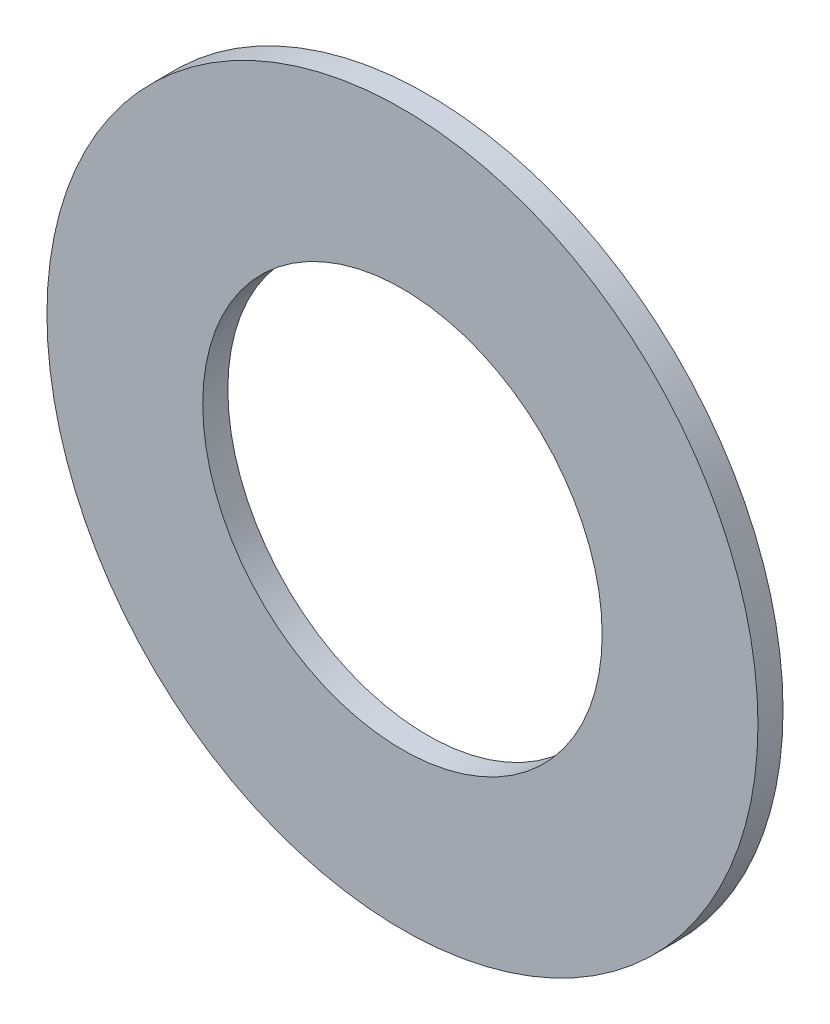
SolidWorks part; units mm, degrees
ref_plane "Front Plane" through (0, 0, 0) normal (0, 0, 1) x (1, 0, 0)
ref_plane "Top Plane" through (0, 0, 0) normal (0, 1, 0) x (1, 0, 0)
ref_plane "Right Plane" through (0, 0, 0) normal (1, 0, 0) x (0, 0, -1)
sketch "Sketch1" plane through (0, 0, 0) normal (0, 0, 1) x (1, 0, 0)
  circle A0 centre (0, 0) radius 12.5 construction
  circle A1 centre (0, 0) radius 22.25 construction
  point P4 (0, -12.5)
  dimension "ID" = 25
  dimension "OD" = 44.5
sketch "Sketch2" plane through (0, 0, 0) normal (1, 0, 0) x (0, 0, -1)
  line L0 (0, -22.25) -> (1.57, -22.25) construction
  dimension "Thickness" = 1.57
sketch "Sketch3" plane through (0, 0, 0) normal (0, 0, 1) x (1, 0, 0)
  circle A0 centre (0, 0) radius 22.25 construction
  circle A1 centre (0, 0) radius 22.25
  circle A2 centre (0, 0) radius 12.5 construction
  circle A3 centre (0, 0) radius 12.5
extrude "Boss-Extrude1" add sketch "Sketch3" against normal blind 1.57
ref_axis "Center Axis 1" through (0, 0, -1.6485) along (0, 0, 1)
equation "\"D1@Boss-Extrude1\"=\"Thickness@Sketch2\""
